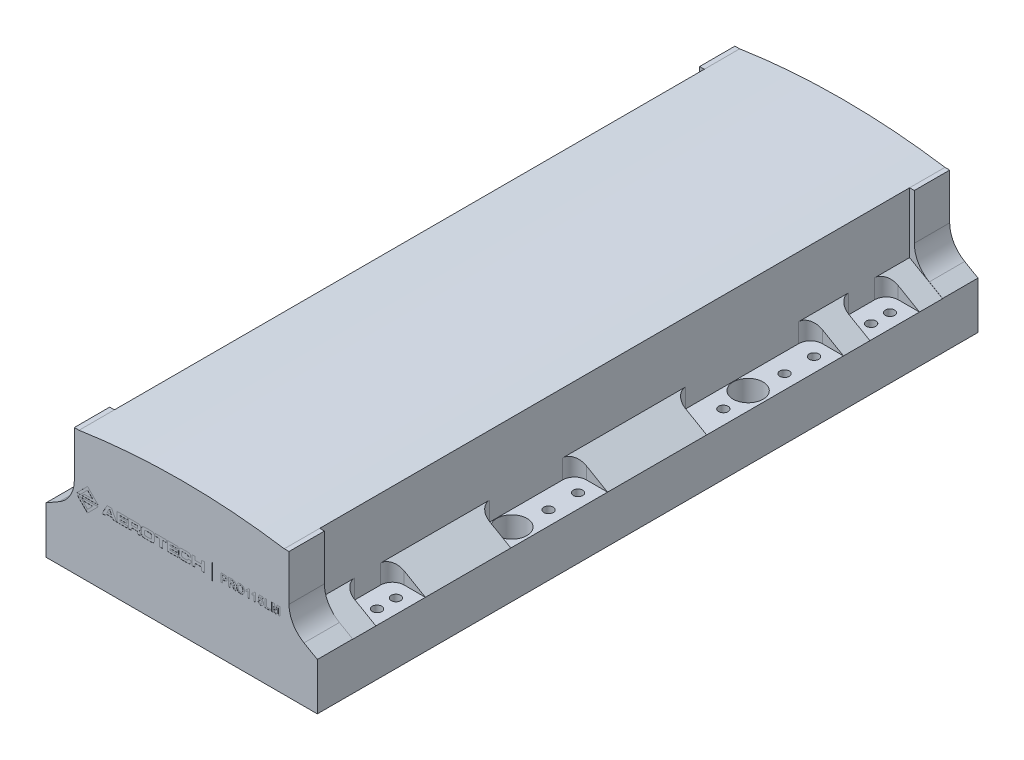
SolidWorks part; units mm, degrees
material "6061 Alloy"
ref_plane "Front" through (0, 0, 0) normal (0, 0, 1) x (1, 0, 0)
ref_plane "Top" through (0, 0, 0) normal (0, 1, 0) x (1, 0, 0)
ref_plane "Right" through (0, 0, 0) normal (1, 0, 0) x (0, 0, -1)
ref_plane "Plane1" through (0, 0, -7.24) normal (0, 0, 1) x (1, 0, 0)
sketch "Sketch1" plane through (0, 0, 0) normal (0, 0, 1) x (1, 0, 0)
  line L0 (-57.5, 0) -> (57.5, 0)
  line L1 (57.5, 0) -> (57.5, 20.9171)
  line L3 (43.5, 29) -> (43.5, 54.6346)
  line L5 (0, 0) -> (0, 146.388) construction
  line L6 (-43.5, 29) -> (-43.5, 54.6346)
  line L7 (43.5, 29) -> (57.5, 20.9171)
  line L8 (-57.5, 0) -> (-57.5, 20.9171)
  line L9 (-43.5, 29) -> (-57.5, 20.9171)
  arc A0 (43.5, 54.6346) -> (-43.5, 54.6346) centre (0, -228.22) ccw
  point P9 (0, 57.96)
  dimension "D7" = 572.36
  dimension "D1" = 115
  dimension "D2" = 60
  dimension "D4" = 29
  dimension "D5" = 87
  dimension "D6" = 60
  dimension "D8" = 228.22
extrude "Base" add sketch "Sketch1" along normal mid plane 250
ref_plane "Plane2" through (0, 57.96, 0) normal (0, 1, 0) x (1, 0, 0)
sketch "Sketch84" plane through (0, 57.96, 0) normal (0, 1, 0) x (-1, 0, 0)
  line L0 (0, 125) -> (0, -125) construction
  line L3 (0, 0) -> (-57.5, 0) construction
  line L6 (-57.5, 125) -> (-57.5, -125) construction
  circle A0 centre (-50, 50) radius 3.3782
  circle A1 centre (50, 50) radius 3.3782
  circle A2 centre (50, -50) radius 3.3782
  circle A3 centre (-50, -50) radius 3.3782
  dimension "D1" = 6.7564
  dimension "D2" = 50
  dimension "D3" = 100
extrude "Cut-Extrude17" cut sketch "Sketch84" against normal through all
sketch "Sketch121" plane through (0, 57.96, 0) normal (0, 1, 0) x (1, 0, 0)
  line L0 (0, 125) -> (0, -125) construction
  line L1 (0, 0) -> (-58.1047, 0) construction
  circle A0 centre (50, 100) radius 3.3782
  circle A1 centre (-50, 100) radius 3.3782
  dimension "D1" = 6.7564
  dimension "D2" = 100
  dimension "D3" = 100
extrude "Cut-Extrude33" [suppressed] cut sketch "Sketch121" against normal through all
sketch "Sketch85" [suppressed] plane through (0, 57.96, 0) normal (0, 1, 0) x (-1, 0, 0)
  line L4 (0, 125) -> (0, -125) construction
  circle A0 centre (-50, -100) radius 6.35
  circle A2 centre (50, -100) radius 6.35
  dimension "D1" = 12.7
extrude "Cut-Extrude18" [suppressed] cut sketch "Sketch85" against normal offset from surface (49.96 mm away) 8
pattern_linear "LPattern3" [suppressed] count 2 spacing 50
mirror "Mirror3" [suppressed] about plane through (0, 0, 0) normal (0, 0, 1)
sketch "Sketch119" plane through (0, 57.96, 0) normal (0, 1, 0) x (1, 0, 0)
  line L0 (-50.8, 50.8) -> (50.8, -50.8) construction
  line L1 (-50.8, 50.8) -> (50.8, 50.8) construction
  line L2 (-50.8, 50.8) -> (-50.8, -50.8) construction
  line L3 (-50.8, -50.8) -> (50.8, -50.8) construction
  line L4 (50.8, 50.8) -> (50.8, -50.8) construction
  circle A0 centre (50.8, 50.8) radius 3.38
  circle A1 centre (-50.8, 50.8) radius 3.38
  circle A2 centre (-50.8, -50.8) radius 3.38
  circle A3 centre (50.8, -50.8) radius 3.38
  dimension "D1" = 6.76
  dimension "D2" = 101.6
extrude "Cut-Extrude31" cut sketch "Sketch119" against normal through all
sketch "Sketch120" plane through (0, 57.96, 0) normal (0, 1, 0) x (1, 0, 0)
  line L0 (-57.5, -125) -> (-57.5, 125) construction
  line L3 (0, 0) -> (-60.7636, 0) construction
  line L5 (0, -113.1077) -> (0, 113.1077) construction
  circle A0 centre (-50.8, 50.8) radius 4.765 construction
  circle A1 centre (-50, 50) radius 5 construction
  circle A2 centre (-50.8, 50.8) radius 5.27 construction
  circle A3 centre (-50.01, 50.0636) radius 6.35
  circle A4 centre (50.01, 50.0636) radius 6.35
  circle A5 centre (-50.01, -50.0636) radius 6.35
  circle A6 centre (50.01, -50.0636) radius 6.35
  dimension "D2" = 9.53
  dimension "D3" = 10
  dimension "D4" = 10.54
  dimension "D5" = 12.7
  dimension "D6" = 1.14
extrude "Cut-Extrude32" cut sketch "Sketch120" against normal offset from surface (49.96 mm away) 8 up to face at (50.4006, 0, -50.4006)
hole_wizard "CBORE for 1/4 Socket Head Cap Screw1" [suppressed] positions "Sketch136" profile "Sketch137" counterbore size "1/4" standard "ANSI Inch"
sketch "Sketch136" plane through (0, 57.96, 0) normal (0, 1, 0) x (1, 0, 0)
  line L0 (0, 135.5467) -> (0, 0) construction
  line L1 (0, 0) -> (-73.2487, 0) construction
  point P0 (-50.8, 177.8)
  point P9 (50.8, 177.8)
  point P10 (50.8, -177.8)
  point P11 (-50.8, -177.8)
  dimension "D1" = 101.6
  dimension "D2" = 457.2
sketch "Sketch137" plane through (-50.8, 57.96, -177.8) normal (1, 0, 0) x (0, 0, 1)
  line L0 (0, 0) -> (0, 57.96)
  line L1 (0, 57.96) -> (3.3782, 57.96)
  line L3 (3.3782, 57.96) -> (3.3782, 49.96)
  line L4 (3.3782, 49.96) -> (5.2451, 49.96)
  line L5 (5.2451, 49.96) -> (5.2451, 0)
  line L7 (5.2451, 0) -> (0, 0)
  line L11 (0, -6.35) -> (0, 107.95) construction
  dimension "Thru Hole Dia." = 6.7564
  dimension "Thru Hole Depth" = 57.96
  dimension "C'Bore Dia." = 10.4902
  dimension "C'Bore Depth" = 49.96
hole_wizard "CBORE for 1/4 Socket Head Cap Screw2" [suppressed] positions "Sketch138" profile "Sketch139" counterbore size "1/4" standard "ANSI Inch"
sketch "Sketch138" plane through (0, 57.96, 0) normal (0, -1, 0) x (-1, 0, 0)
  line L0 (0, -99.0681) -> (0, 0) construction
  line L1 (0, 0) -> (-32.0031, 0) construction
  point P0 (-50.8, 330.2)
  point P9 (50.8, 330.2)
  point P13 (50.8, -330.2)
  point P14 (-50.8, -330.2)
  dimension "D1" = 101.6
  dimension "D2" = 660.4
sketch "Sketch139" plane through (50.8, 57.96, -330.2) normal (1, 0, 0) x (0, 0, 1)
  line L0 (0, 0) -> (0, 57.96)
  line L1 (0, 57.96) -> (3.3782, 57.96)
  line L3 (3.3782, 57.96) -> (3.3782, 49.96)
  line L4 (3.3782, 49.96) -> (5.2451, 49.96)
  line L5 (5.2451, 49.96) -> (5.2451, 0)
  line L7 (5.2451, 0) -> (0, 0)
  line L11 (0, -6.35) -> (0, 107.95) construction
  dimension "Thru Hole Dia." = 6.7564
  dimension "Thru Hole Depth" = 57.96
  dimension "C'Bore Dia." = 10.4902
  dimension "C'Bore Depth" = 49.96
sketch "Sketch23" plane through (0, 0, 125) normal (0, 0, 1) x (1, 0, 0)
  line L0 (-15, 0) -> (15, 0)
  line L1 (-15, 1) -> (15, 1)
  line L2 (-57.5, 0) -> (57.5, 0) construction
  line L3 (0, 0) -> (0, 32.8248) construction
  line L4 (15, 1) -> (15, 0)
  line L5 (-15, 1) -> (-15, 0)
  dimension "D1" = 1
  dimension "D2" = 30
extrude "Lower Pads" cut sketch "Sketch23" against normal through all
sketch "Sketch86" plane through (0, 0, 125) normal (0, 0, 1) x (1, 0, 0)
  line L0 (-57.5, 54.6346) -> (-43.5, 54.6346)
  line L1 (-57.5, 1.021) -> (57.5, 1.021)
  line L2 (-57.5, 1.021) -> (-57.5, 54.6346)
  line L4 (57.5, 1.021) -> (57.5, 54.6346)
  line L5 (-57.5, 0) -> (-15, 0) construction
  line L7 (43.5, 54.6346) -> (57.5, 54.6346)
  line L8 (0, 0) -> (0, 61.021) construction
  line L9 (-57.5, 20.9171) -> (-57.5, 0) construction
  line L10 (57.5, 0) -> (57.5, 20.9171) construction
  arc A0 (43.5, 54.6346) -> (-43.5, 54.6346) centre (0, -228.22) ccw
  arc A1 (43.5, 54.6346) -> (-43.5, 54.6346) centre (0, -228.22) ccw construction
  dimension "D5" = 1.021
extrude "Extrude1" add sketch "Sketch86" along normal blind 15
sketch "Sketch87" plane through (0, 0, -125) normal (0, 0, -1) x (-1, 0, 0)
  line L0 (57.5, 20.9171) -> (57.5, 0) construction
  line L1 (-57.5, 54.6346) -> (-43.5, 54.6346)
  line L2 (-57.5, 54.6346) -> (-57.5, 1.021)
  line L3 (-57.5, 1.021) -> (57.5, 1.021)
  line L4 (57.5, 54.6346) -> (57.5, 1.021)
  line L5 (57.5, 1.021) -> (-57.5, 1.021) construction
  line L6 (43.5, 54.6346) -> (57.5, 54.6346)
  arc A0 (43.5, 54.6346) -> (-43.5, 54.6346) centre (0, -228.22) ccw
  arc A1 (43.5, 54.6346) -> (-43.5, 54.6346) centre (0, -228.22) ccw construction
extrude "Extrude2" add sketch "Sketch87" along normal blind 15
sketch "Sketch97" plane through (0, 57.96, 0) normal (0, 1, 0) x (-1, 0, 0)
  line L0 (57.5, 125) -> (57.5, -125) construction
  line L1 (57.5, -25) -> (48.5, -25)
  line L2 (57.5, -25) -> (57.5, -83)
  line L3 (57.5, -83) -> (48.5, -83)
  line L4 (43.5, -30) -> (43.5, -78)
  line L5 (43.5, 125) -> (43.5, -125) construction
  line L6 (0, 0) -> (-57.5, 0) construction
  line L7 (-57.5, 125) -> (-57.5, -125) construction
  line L8 (0, 0) -> (0, -140) construction
  line L9 (-43.5, -140) -> (-57.5, -140) construction
  line L11 (-43.5, -30) -> (-43.5, -78)
  line L12 (-57.5, -83) -> (-48.5, -83)
  line L13 (-57.5, -25) -> (-57.5, -83)
  line L14 (-57.5, -25) -> (-48.5, -25)
  line L15 (-57.5, 17) -> (-48.5, 17)
  line L16 (-57.5, 17) -> (-57.5, 58)
  line L17 (-57.5, 58) -> (-48.5, 58)
  line L18 (-43.5, 22) -> (-43.5, 53)
  line L19 (43.5, 22) -> (43.5, 53)
  line L20 (57.5, 58) -> (48.5, 58)
  line L21 (57.5, 17) -> (57.5, 58)
  line L22 (57.5, 17) -> (48.5, 17)
  arc A0 (43.5, -78) -> (48.5, -83) centre (48.5, -78) ccw
  arc A1 (43.5, -30) -> (48.5, -25) centre (48.5, -30) cw
  arc A2 (-43.5, -30) -> (-48.5, -25) centre (-48.5, -30) ccw
  arc A3 (-43.5, -78) -> (-48.5, -83) centre (-48.5, -78) cw
  arc A4 (-43.5, 53) -> (-48.5, 58) centre (-48.5, 53) ccw
  arc A5 (-43.5, 22) -> (-48.5, 17) centre (-48.5, 22) cw
  arc A6 (43.5, 22) -> (48.5, 17) centre (48.5, 22) ccw
  arc A7 (43.5, 53) -> (48.5, 58) centre (48.5, 53) cw
  dimension "D3" = 5
  dimension "D1" = 25
  dimension "D2" = 83
  dimension "D4" = 17
  dimension "D5" = 58
extrude "Cut-Extrude21" cut sketch "Sketch97" against normal up to vertex (54.671 mm away)
sketch "Sketch98" plane through (0, 0, 140) normal (0, 0, 1) x (1, 0, 0)
  line L0 (57.5, 54.6346) -> (45.5, 54.6346)
  line L1 (57.5, 54.6346) -> (43.5, 54.6346) construction
  line L2 (45.5, 54.6346) -> (45.5, 27.9282)
  line L3 (45.5, 27.9282) -> (57.5, 21)
  line L4 (57.5, 1.021) -> (57.5, 54.6346) construction
  line L5 (57.5, 21) -> (57.5, 54.6346)
  line L6 (15, 0) -> (57.5, 0) construction
  line L7 (0, 0) -> (0, 57.96) construction
  line L9 (-57.5, 21) -> (-57.5, 54.6346)
  line L10 (-45.5, 27.9282) -> (-57.5, 21)
  line L11 (-45.5, 54.6346) -> (-45.5, 27.9282)
  line L12 (-57.5, 54.6346) -> (-45.5, 54.6346)
  arc A0 (43.5, 54.6346) -> (-43.5, 54.6346) centre (0, -228.22) ccw construction
  dimension "D1" = 12
  dimension "D2" = 21
  dimension "D3" = 120
extrude "Cut-Extrude22" cut sketch "Sketch98" against normal through all
fillet "Fillet1" radius 12.7 4 edges at (-45.5, 27.9282, 132.5) (-45.5, 27.9282, -132.5) (45.5, 27.9282, -132.5) (45.5, 27.9282, 132.5)
chamfer "Chamfer1" distance 1 angle 45 4 edges at (-15, 0, 0) (15, 0, 0) (-57.5, 0, 0) (57.5, 0, 0)
sketch "Sketch103" [suppressed] plane through (0, 57.96, 0) normal (0, 1, 0) x (1, 0, 0)
  line L0 (-50, 0) -> (50, 0) construction
  line L1 (-57.5, -17) -> (-57.5, 25) construction
  circle A0 centre (-50, 0) radius 6.35
  circle A1 centre (50, 0) radius 6.35
  dimension "D1" = 12.7
  dimension "D2" = 7.5
extrude "Cut-Extrude26" [suppressed] cut sketch "Sketch103" against normal up to surface (49.96 mm away)
sketch "Sketch104" [suppressed] plane through (0, 8, 0) normal (0, 1, 0) x (1, 0, 0)
  circle A0 centre (50, 0) radius 3.3782
  circle A1 centre (-50, 0) radius 3.3782
  circle A3 centre (50, 50) radius 3.3782 construction
extrude "Cut-Extrude27" [suppressed] cut sketch "Sketch104" against normal through all
sketch "Sketch107" plane through (0, 1, 0) normal (0, -1, 0) x (1, 0, 0)
  circle A0 centre (0, 0) radius 4.007
  dimension "D1" = 8.014
extrude "Cut-Extrude30" cut sketch "Sketch107" against normal blind 9
pattern_linear "LPattern2" count 4 spacing 25 along (0, 0, 1) of "Cut-Extrude30"
mirror "Mirror2" about plane through (0, 0, 0) normal (0, 0, 1) of "LPattern2"
hole_wizard "M4x0.7 Tapped Hole2" positions "Sketch109" profile "Sketch108" tap size "M4x0.7" standard "ANSI Metric"
sketch "Sketch109" plane through (0, 20.9171, 0) normal (0, 1, 0) x (-1, 0, 0)
  line L5 (0, 0) -> (116.5246, 0) construction
  line L8 (0, 129.449) -> (0, -129.449) construction
  line L10 (51.5, -76.5) -> (51.5, -64) construction
  line L16 (57.5, -83) -> (57.5, -25) construction
  line L18 (-51.5, -76.5) -> (-51.5, -64) construction
  line L19 (-51.5, 36) -> (-51.5, 23.5) construction
  line L22 (51.5, 36) -> (51.5, 23.5) construction
  point P23 (51.5, -64)
  point P48 (51.5, -76.5)
  point P75 (-51.5, -76.5)
  point P76 (-51.5, -64)
  point P77 (-51.5, 36)
  point P78 (-51.5, 23.5)
  point P83 (51.5, 36)
  point P84 (51.5, 23.5)
  dimension "D1" = 12.5
  dimension "D3" = 6
  dimension "D4" = 23.5
  dimension "D2" = 64
sketch "Sketch108" plane through (-51.5, 20.9171, -64) normal (1, 0, 0) x (0, 0, 1)
  line L0 (0, 0) -> (0, 13.0914)
  line L1 (0, 13.0914) -> (1.65, 12.1)
  line L2 (1.65, 12.1) -> (1.65, 10)
  line L3 (1.65, 10) -> (2, 10)
  line L4 (2, 10) -> (2, 0)
  line L5 (2, 0) -> (0, 0)
  line L10 (0, 13.0914) -> (-1.65, 12.1) construction
  line L11 (0, -6.35) -> (0, 107.95) construction
  dimension "Tap Drill Dia." = 3.3
  dimension "Tap Drill Depth" = 12.1
  dimension "Thread Major Dia." = 4
  dimension "Thread Depth" = 10
  dimension "Drill Angle" = 118
sketch "Sketch122" plane through (0, 57.96, 0) normal (0, 1, 0) x (1, 0, 0)
  line L0 (-43.5, -125) -> (-43.5, 125) construction
  line L1 (-57.5, 115.2) -> (-48.5, 115.2)
  line L2 (-57.5, 115.2) -> (-57.5, 94.2)
  line L3 (-57.5, 94.2) -> (-48.5, 94.2)
  line L4 (-43.5, 110.2) -> (-43.5, 99.2)
  line L7 (0, 0) -> (-171.2058, 0) construction
  line L8 (-57.5, 83) -> (-57.5, 25) construction
  line L9 (0, -271.3829) -> (0, 271.3829) construction
  line L16 (57.5, 94.2) -> (48.5, 94.2)
  line L17 (57.5, 115.2) -> (48.5, 115.2)
  line L22 (43.5, 110.2) -> (43.5, 99.2)
  line L24 (57.5, 115.2) -> (57.5, 94.2)
  line L28 (57.5, -115.2) -> (48.5, -115.2)
  line L29 (57.5, -115.2) -> (57.5, -94.2)
  line L30 (57.5, -94.2) -> (48.5, -94.2)
  line L31 (43.5, -110.2) -> (43.5, -99.2)
  line L38 (-57.5, -94.2) -> (-48.5, -94.2)
  line L39 (-57.5, -115.2) -> (-48.5, -115.2)
  line L44 (-43.5, -110.2) -> (-43.5, -99.2)
  line L46 (-57.5, -115.2) -> (-57.5, -94.2)
  arc A0 (48.5, -94.2) -> (43.5, -99.2) centre (48.5, -99.2) ccw
  arc A1 (48.5, -115.2) -> (43.5, -110.2) centre (48.5, -110.2) cw
  arc A2 (-48.5, -115.2) -> (-43.5, -110.2) centre (-48.5, -110.2) ccw
  arc A3 (-48.5, -94.2) -> (-43.5, -99.2) centre (-48.5, -99.2) cw
  arc A4 (48.5, 94.2) -> (43.5, 99.2) centre (48.5, 99.2) cw
  arc A5 (48.5, 115.2) -> (43.5, 110.2) centre (48.5, 110.2) ccw
  arc A6 (-48.5, 94.2) -> (-43.5, 99.2) centre (-48.5, 99.2) ccw
  arc A7 (-48.5, 115.2) -> (-43.5, 110.2) centre (-48.5, 110.2) cw
  point P35 (43.5, -94.2)
  point P38 (43.5, -115.2)
  point P41 (-43.5, -115.2)
  point P44 (-43.5, -94.2)
  point P47 (43.5, 94.2)
  point P50 (43.5, 115.2)
  point P53 (-43.5, 94.2)
  point P56 (-43.5, 115.2)
  dimension "D3" = 5
  dimension "D2" = 94.2
  dimension "D4" = 115.2
extrude "Cut-Extrude34" cut sketch "Sketch122" against normal up to surface (37.0429 mm away) up to face at (-51.5, 20.9171, -62)
hole_wizard "M4x0.7 Tapped Hole5" positions "Sketch124" profile "Sketch123" tap size "M4x0.7" standard "ANSI Metric"
sketch "Sketch124" plane through (0, 20.9171, 0) normal (0, 1, 0) x (1, 0, 0)
  line L2 (-51.5, 108.7) -> (-51.5, 100.7) construction
  line L6 (-57.5, 94.2) -> (-57.5, 115.2) construction
  line L8 (0, 0) -> (-155.8698, 0) construction
  line L11 (0, 0) -> (0, 209.1535) construction
  line L12 (-57.5, 115.2) -> (-48.5, 115.2) construction
  point P0 (-51.5, 108.7)
  point P2 (-51.5, 100.7)
  point P33 (51.5, 100.7)
  point P34 (51.5, 108.7)
  point P36 (-51.5, -108.7)
  point P37 (-51.5, -100.7)
  point P38 (51.5, -108.7)
  point P39 (51.5, -100.7)
  dimension "D1" = 8
  dimension "D2" = 6
  dimension "D3" = 6.5
sketch "Sketch123" plane through (-51.5, 20.9171, -108.7) normal (1, 0, 0) x (0, 0, 1)
  line L0 (0, 0) -> (0, 13.0914)
  line L1 (0, 13.0914) -> (1.65, 12.1)
  line L2 (1.65, 12.1) -> (1.65, 10)
  line L3 (1.65, 10) -> (2, 10)
  line L4 (2, 10) -> (2, 0)
  line L5 (2, 0) -> (0, 0)
  line L10 (0, 13.0914) -> (-1.65, 12.1) construction
  line L11 (0, -6.35) -> (0, 107.95) construction
  dimension "Tap Drill Dia." = 3.3
  dimension "Tap Drill Depth" = 12.1
  dimension "Thread Major Dia." = 4
  dimension "Thread Depth" = 10
  dimension "Drill Angle" = 118
sketch "Sketch115" plane through (0, 57.96, 0) normal (0, 1, 0) x (1, 0, 0)
  line L0 (-51.85, 125) -> (-57.5, 125) construction
  line L1 (-57.5, -89.5) -> (-43.5, -89.5)
  line L2 (-57.5, -89.5) -> (-57.5, -115)
  line L3 (-57.5, -115) -> (-43.5, -115)
  line L4 (-43.5, -89.5) -> (-43.5, -115)
  line L7 (0, 0) -> (-69.7916, 0) construction
  line L8 (-43.5, 89.5) -> (-43.5, 115)
  line L9 (-57.5, 115) -> (-43.5, 115)
  line L10 (-57.5, 89.5) -> (-57.5, 115)
  line L11 (-57.5, 89.5) -> (-43.5, 89.5)
  line L12 (0, 0) -> (0, -483.8343) construction
  line L13 (57.5, 89.5) -> (43.5, 89.5)
  line L14 (57.5, 89.5) -> (57.5, 115)
  line L15 (57.5, 115) -> (43.5, 115)
  line L16 (43.5, 89.5) -> (43.5, 115)
  line L17 (43.5, -89.5) -> (43.5, -115)
  line L18 (57.5, -115) -> (43.5, -115)
  line L19 (57.5, -89.5) -> (57.5, -115)
  line L20 (57.5, -89.5) -> (43.5, -89.5)
  line L21 (43.5, -22) -> (43.5, -53) construction
  line L22 (57.5, -125) -> (57.5, -115.2) construction
  dimension "D1" = 10
  dimension "D2" = 25.5
extrude "Extrude7" [suppressed] cut sketch "Sketch115" against normal up to surface (37.0429 mm away)
fillet "Fillet2" [suppressed] radius 5
hole_wizard "M4x0.7 Tapped Hole4" [suppressed] positions "Sketch116" profile "Sketch117" tap size "M4x0.7" standard "ANSI Metric"
sketch "Sketch116" [suppressed] plane through (0, 20.9171, 0) normal (0, 1, 0) x (-1, 0, 0)
  line L0 (-51.5, -76.5) -> (-51.5, -64) construction
  line L2 (-51.5, 221) -> (-51.5, 233.5) construction
  line L7 (0, -97.8) -> (0, 0) construction
  line L8 (0, 0) -> (-90.3431, 0) construction
  line L9 (-48.5, 214.5) -> (-57.5, 214.5) construction
  point P0 (-51.5, 221)
  point P5 (-51.5, 233.5)
  point P49 (51.5, 233.5)
  point P50 (51.5, 221)
  point P51 (-51.5, -233.5)
  point P52 (-51.5, -221)
  point P53 (51.5, -233.5)
  point P54 (51.5, -221)
  dimension "D1" = 6.5
sketch "Sketch117" plane through (51.5, 20.9171, 221) normal (1, 0, 0) x (0, 0, 1)
  line L0 (0, 0) -> (0, 13.0914)
  line L1 (0, 13.0914) -> (1.65, 12.1)
  line L2 (1.65, 12.1) -> (1.65, 10)
  line L3 (1.65, 10) -> (2, 10)
  line L4 (2, 10) -> (2, 0)
  line L5 (2, 0) -> (0, 0)
  line L10 (0, 13.0914) -> (-1.65, 12.1) construction
  line L11 (0, -6.35) -> (0, 107.95) construction
  dimension "Tap Drill Dia." = 3.3
  dimension "Tap Drill Depth" = 12.1
  dimension "Thread Major Dia." = 4
  dimension "Thread Depth" = 10
  dimension "Drill Angle" = 118
hole_wizard "M4x0.7 Tapped Hole6" positions "Sketch134" profile "Sketch133" tap size "M4x0.7" standard "ANSI Metric"
sketch "Sketch134" plane through (0, 20.9171, 0) normal (0, 1, 0) x (-1, 0, 0)
  point P0 (-51.5, -38.0746)
  point P2 (51.5, -38.0746)
  dimension "D1" = 38.0746
sketch "Sketch133" plane through (51.5, 20.9171, -38.0746) normal (1, 0, 0) x (0, 0, 1)
  line L0 (0, 0) -> (0, 11.0914)
  line L1 (0, 11.0914) -> (1.65, 10.1)
  line L2 (1.65, 10.1) -> (1.65, 8)
  line L3 (1.65, 8) -> (2, 8)
  line L4 (2, 8) -> (2, 0)
  line L5 (2, 0) -> (0, 0)
  line L10 (0, 11.0914) -> (-1.65, 10.1) construction
  line L11 (0, -6.35) -> (0, 107.95) construction
  dimension "Tap Drill Dia." = 3.3
  dimension "Tap Drill Depth" = 10.1
  dimension "Thread Major Dia." = 4
  dimension "Thread Depth" = 8
  dimension "Drill Angle" = 118
ref_plane "Neg Elec Limit" through (0, 0, 30) normal (0, 0, 1) x (1, 0, 0)
ref_plane "Neg Hard Stop" through (0, 0, 37.5) normal (0, 0, 1) x (1, 0, 0)
ref_plane "Neg Nominal Travel Limit" through (0, 0, 25) normal (0, 0, 1) x (1, 0, 0)
ref_plane "Pos Nominal Travel Limit" through (0, 0, -25) normal (0, 0, 1) x (1, 0, 0)
ref_plane "Pos Elec Limit" through (0, 0, -30) normal (0, 0, 1) x (1, 0, 0)
ref_plane "Pos Hard Stop" through (0, 0, -37.5) normal (0, 0, 1) x (1, 0, 0)
sketch "Sketch140" plane through (0, 0, 140) normal (0, 0, 1) x (1, 0, 0)
  line L0 (9.7306, 30.9175) -> (12.9223, 30.9175) construction
  line L1 (-33.783, 28.9203) -> (137.8803, 28.9203) construction
  line L2 (-1.3394, 148.5268) -> (-1.3394, 202.5426) construction
  line L3 (16.3009, 30.9523) -> (13.1692, 30.9523) construction
  line L4 (-44.3894, 35.8141) -> (41.7106, 35.8141) construction
  line L5 (-44.3894, 35.8141) -> (-44.3894, 26.021) construction
  line L6 (-44.3894, 26.021) -> (41.7106, 26.021) construction
  line L7 (41.7106, 35.8141) -> (41.7106, 26.021) construction
  line L9 (-57.5, 1.021) -> (57.5, 1.021) construction
  text T0 "<b>PRO115LM</b>" font "Arial" height 3.5
  point P10 (-1.2589, 30.8909)
  point P13 (-1.3394, 26.021)
  line B0 (-39.9006, 26.021) -> (-35.3807, 30.5877)
  line B1 (-35.3807, 30.5877) -> (-42.2558, 30.5668)
  line B2 (-42.2558, 30.5668) -> (-41.2744, 29.5804)
  line B3 (-41.2744, 29.5804) -> (-37.7053, 29.596)
  line B4 (-37.7053, 29.596) -> (-39.9056, 27.4109)
  line B5 (-39.9056, 27.4109) -> (-43.0364, 30.5668)
  line B6 (-43.0364, 30.5668) -> (-44.3894, 30.5617)
  line B7 (-44.3894, 30.5617) -> (-39.9006, 26.021)
  line B8 (-39.9006, 35.8141) -> (-35.3807, 31.2476)
  line B9 (-35.3807, 31.2476) -> (-42.2558, 31.2686)
  line B10 (-42.2558, 31.2686) -> (-41.2744, 32.255)
  line B11 (-41.2744, 32.255) -> (-37.7053, 32.2392)
  line B12 (-37.7053, 32.2392) -> (-39.9056, 34.4244)
  line B13 (-39.9056, 34.4244) -> (-43.0364, 31.2686)
  line B14 (-43.0364, 31.2686) -> (-44.3894, 31.2735)
  line B15 (-44.3894, 31.2735) -> (-39.9006, 35.8141)
  line B16 (-28.9992, 28.9203) -> (-29.3465, 29.5948)
  line B17 (-29.3465, 29.5948) -> (-32.0262, 29.5948)
  line B18 (-32.0262, 29.5948) -> (-32.3735, 28.9203)
  line B19 (-32.3735, 28.9203) -> (-33.783, 28.9203)
  line B20 (-33.783, 28.9203) -> (-31.6346, 32.9147)
  line B21 (-31.6346, 32.9147) -> (-29.7174, 32.9147)
  line B22 (-29.7174, 32.9147) -> (-27.5984, 28.9203)
  line B23 (-27.5984, 28.9203) -> (-28.9992, 28.9203)
  line B24 (-29.7796, 30.4717) -> (-30.5602, 31.9855)
  line B25 (-30.5602, 31.9855) -> (-30.8064, 31.9855)
  line B26 (-30.8064, 31.9855) -> (-31.5871, 30.4717)
  line B27 (-31.5871, 30.4717) -> (-29.7796, 30.4717)
  line B28 (-27.3996, 32.9147) -> (-22.9105, 32.9147)
  line B29 (-22.9105, 32.9147) -> (-22.9105, 31.9781)
  line B30 (-22.9105, 31.9781) -> (-26.1855, 31.9781)
  line B31 (-26.1855, 31.9781) -> (-26.1855, 31.401)
  line B32 (-26.1855, 31.401) -> (-23.0754, 31.401)
  line B33 (-23.0754, 31.401) -> (-23.0754, 30.5243)
  line B34 (-23.0754, 30.5243) -> (-26.1855, 30.5243)
  line B35 (-26.1855, 30.5243) -> (-26.1855, 29.872)
  line B36 (-26.1855, 29.872) -> (-22.8879, 29.872)
  line B37 (-22.8879, 29.872) -> (-22.8879, 28.9203)
  line B38 (-22.8879, 28.9203) -> (-27.3996, 28.9203)
  line B39 (-27.3996, 28.9203) -> (-27.3996, 32.9147)
  line B40 (-22.4845, 28.9203) -> (-22.4845, 32.9147)
  line B41 (-22.4845, 32.9147) -> (-19.5008, 32.9147)
  line B42 (-17.4858, 29.2903) -> (-17.4858, 28.9203)
  line B43 (-17.4858, 28.9203) -> (-18.6998, 28.9203)
  line B44 (-18.6998, 28.9203) -> (-18.6998, 29.1301)
  line B45 (-19.5097, 29.9321) -> (-21.2478, 29.9321)
  line B46 (-21.2478, 29.9321) -> (-21.2478, 28.9203)
  line B47 (-21.2478, 28.9203) -> (-22.4845, 28.9203)
  line B48 (-21.2478, 30.9288) -> (-19.5127, 30.9288)
  line B49 (-19.5156, 31.9181) -> (-21.2478, 31.9181)
  line B50 (-21.2478, 31.9181) -> (-21.2478, 30.9288)
  line B51 (-11.261, 32.9147) -> (-6.3593, 32.9147)
  line B52 (-6.3593, 32.9147) -> (-6.3593, 31.8956)
  line B53 (-6.3593, 31.8956) -> (-8.1582, 31.8956)
  line B54 (-8.1582, 31.8956) -> (-8.1582, 28.9203)
  line B55 (-8.1582, 28.9203) -> (-9.4547, 28.9203)
  line B56 (-9.4547, 28.9203) -> (-9.4547, 31.8956)
  line B57 (-9.4547, 31.8956) -> (-11.261, 31.8956)
  line B58 (-11.261, 31.8956) -> (-11.261, 32.9147)
  line B59 (-6.0733, 32.9147) -> (-1.5843, 32.9147)
  line B60 (-1.5843, 32.9147) -> (-1.5843, 31.9781)
  line B61 (-1.5843, 31.9781) -> (-4.8593, 31.9781)
  line B62 (-4.8593, 31.9781) -> (-4.8593, 31.401)
  line B63 (-4.8593, 31.401) -> (-1.7492, 31.401)
  line B64 (-1.7492, 31.401) -> (-1.7492, 30.5243)
  line B65 (-1.7492, 30.5243) -> (-4.8593, 30.5243)
  line B66 (-4.8593, 30.5243) -> (-4.8593, 29.872)
  line B67 (-4.8593, 29.872) -> (-1.5618, 29.872)
  line B68 (-1.5618, 29.872) -> (-1.5618, 28.9203)
  line B69 (-1.5618, 28.9203) -> (-6.0733, 28.9203)
  line B70 (-6.0733, 28.9203) -> (-6.0733, 32.9147)
  line B71 (2.6755, 30.4642) -> (3.9102, 30.4642)
  line B72 (3.8449, 31.4834) -> (2.6104, 31.4834)
  line B73 (4.3494, 32.9147) -> (5.6461, 32.9147)
  line B74 (5.6461, 32.9147) -> (5.6461, 31.4834)
  line B75 (5.6461, 31.4834) -> (8.4339, 31.4834)
  line B76 (8.4339, 31.4834) -> (8.4339, 32.9147)
  line B77 (8.4339, 32.9147) -> (9.7306, 32.9147)
  line B78 (9.7306, 32.9147) -> (9.7306, 28.9203)
  line B79 (9.7306, 28.9203) -> (8.4339, 28.9203)
  line B80 (8.4339, 28.9203) -> (8.4339, 30.3668)
  line B81 (8.4339, 30.3668) -> (5.6461, 30.3668)
  line B82 (5.6461, 30.3668) -> (5.6461, 28.9203)
  line B83 (5.6461, 28.9203) -> (4.3494, 28.9203)
  line B84 (4.3494, 28.9203) -> (4.3494, 32.9147)
  line B85 (13.1692, 27.4951) -> (12.9223, 27.4951)
  line B86 (12.9223, 27.4951) -> (12.9223, 34.4095)
  line B87 (12.9223, 34.4095) -> (13.1692, 34.4095)
  line B88 (13.1692, 34.4095) -> (13.1692, 27.4951)
  spline B89 degree 3 poles (-19.5008, 32.9147) (-18.8013, 32.9129) (-18.3824, 32.9059) (-18.2441, 32.894) knots 2 2 2 2 3 3 3 3
  spline B90 degree 3 poles (-18.2441, 32.894) (-18.1057, 32.882) (-17.9724, 32.8365) (-17.8438, 32.7571) knots 3 3 3 3 4 4 4 4
  spline B91 degree 3 poles (-17.8438, 32.7571) (-17.6898, 32.666) (-17.5842, 32.5395) (-17.5268, 32.3778) knots 4 4 4 4 5 5 5 5
  spline B92 degree 3 poles (-17.5268, 32.3778) (-17.4695, 32.2162) (-17.4408, 31.9626) (-17.4408, 31.6177) knots 5 5 5 5 6 6 6 6
  spline B93 degree 3 poles (-17.4408, 31.6177) (-17.4408, 31.3261) (-17.459, 31.1117) (-17.4955, 30.9749) knots 6 6 6 6 7 7 7 7
  spline B94 degree 3 poles (-17.4955, 30.9749) (-17.5321, 30.838) (-17.6009, 30.7278) (-17.7016, 30.6445) knots 7 7 7 7 8 8 8 8
  spline B95 degree 3 poles (-17.7016, 30.6445) (-17.8101, 30.5575) (-17.9744, 30.497) (-18.1936, 30.4632) knots 8 8 8 8 9 9 9 9
  spline B96 degree 3 poles (-18.1936, 30.4632) (-17.9351, 30.4432) (-17.7494, 30.3703) (-17.6369, 30.2442) knots 9 9 9 9 10 10 10 10
  spline B97 degree 3 poles (-17.6369, 30.2442) (-17.5716, 30.1688) (-17.5301, 30.077) (-17.5126, 29.9684) knots 10 10 10 10 11 11 11 11
  spline B98 degree 3 poles (-17.5126, 29.9684) (-17.4947, 29.8599) (-17.4858, 29.6338) (-17.4858, 29.2903) knots 11 11 11 11 12 12 12 12
  spline B99 degree 3 poles (-18.6998, 29.1301) (-18.6998, 29.3531) (-18.7082, 29.5119) (-18.7251, 29.6065) knots 15 15 15 15 16 16 16 16
  spline B100 degree 3 poles (-18.7251, 29.6065) (-18.742, 29.7012) (-18.773, 29.7734) (-18.8184, 29.8225) knots 16 16 16 16 17 17 17 17
  spline B101 degree 3 poles (-18.8184, 29.8225) (-18.864, 29.8698) (-18.9268, 29.8999) (-19.0069, 29.9128) knots 17 17 17 17 18 18 18 18
  spline B102 degree 3 poles (-19.0069, 29.9128) (-19.0869, 29.9256) (-19.2547, 29.9321) (-19.5097, 29.9321) knots 18 18 18 18 19 19 19 19
  spline B103 degree 3 poles (-19.5127, 30.9288) (-19.2133, 30.9348) (-19.0348, 30.9402) (-18.977, 30.9453) knots 1 1 1 1 2 2 2 2
  spline B104 degree 3 poles (-18.977, 30.9453) (-18.9192, 30.9501) (-18.8699, 30.9656) (-18.8286, 30.9916) knots 2 2 2 2 3 3 3 3
  spline B105 degree 3 poles (-18.8286, 30.9916) (-18.7759, 31.0234) (-18.7388, 31.0722) (-18.7173, 31.138) knots 3 3 3 3 4 4 4 4
  spline B106 degree 3 poles (-18.7173, 31.138) (-18.6957, 31.2038) (-18.6848, 31.3034) (-18.6848, 31.4369) knots 4 4 4 4 5 5 5 5
  spline B107 degree 3 poles (-18.6848, 31.4369) (-18.6848, 31.5704) (-18.6972, 31.6695) (-18.7217, 31.7343) knots 5 5 5 5 6 6 6 6
  spline B108 degree 3 poles (-18.7217, 31.7343) (-18.7461, 31.799) (-18.7885, 31.8454) (-18.8493, 31.8733) knots 6 6 6 6 7 7 7 7
  spline B109 degree 3 poles (-18.8493, 31.8733) (-18.8924, 31.8932) (-18.9437, 31.9051) (-19.0034, 31.9091) knots 7 7 7 7 8 8 8 8
  spline B110 degree 3 poles (-19.0034, 31.9091) (-19.0632, 31.913) (-19.2339, 31.916) (-19.5156, 31.9181) knots 8 8 8 8 9 9 9 9
  spline B111 degree 3 poles (-16.0997, 32.9093) (-15.7732, 32.9528) (-15.1716, 32.9748) (-14.2949, 32.9748) knots 11 11 11 11 12 12 12 12
  spline B112 degree 3 poles (-16.9695, 32.2465) (-16.8625, 32.6269) (-16.5728, 32.8478) (-16.0997, 32.9093) knots 10 10 10 10 11 11 11 11
  spline B113 degree 3 poles (-16.9695, 29.5858) (-17.0425, 29.8472) (-17.0791, 30.2994) (-17.0791, 30.9413) (-17.0791, 31.5517) (-17.0425, 31.9867) (-16.9695, 32.2465) knots 8 8 8 8 9 9 9 10 10 10 10
  spline B114 degree 3 poles (-16.0997, 28.9198) (-16.5728, 28.9833) (-16.8625, 29.2051) (-16.9695, 29.5858) knots 7 7 7 7 8 8 8 8
  spline B115 degree 3 poles (-12.4903, 28.9198) (-12.8189, 28.8802) (-13.4164, 28.8605) (-14.283, 28.8605) (-15.1658, 28.8605) (-15.7713, 28.8802) (-16.0997, 28.9198) knots 5 5 5 5 6 6 6 7 7 7 7
  spline B116 degree 3 poles (-11.6206, 29.5858) (-11.7276, 29.2051) (-12.0176, 28.9833) (-12.4903, 28.9198) knots 4 4 4 4 5 5 5 5
  spline B117 degree 3 poles (-11.6206, 32.2465) (-11.5473, 31.9847) (-11.5108, 31.5417) (-11.5108, 30.9174) (-11.5108, 30.2913) (-11.5473, 29.8472) (-11.6206, 29.5858) knots 2 2 2 2 3 3 3 4 4 4 4
  spline B118 degree 3 poles (-12.4903, 32.9093) (-12.0176, 32.8478) (-11.7276, 32.6269) (-11.6206, 32.2465) knots 1 1 1 1 2 2 2 2
  spline B119 degree 3 poles (-14.2949, 32.9748) (-13.4206, 32.9748) (-12.8189, 32.9528) (-12.4903, 32.9093) knots 0 0 0 0 1 1 1 1
  spline B120 degree 3 poles (-13.2069, 31.9019) (-13.3572, 31.9227) (-13.7188, 31.9331) (-14.292, 31.9331) knots 13 13 13 13 14 14 14 14
  spline B121 degree 3 poles (-12.8837, 31.7426) (-12.9491, 31.828) (-13.0567, 31.881) (-13.2069, 31.9019) knots 12 12 12 12 13 13 13 13
  spline B122 degree 3 poles (-12.777, 31.4376) (-12.7969, 31.5734) (-12.8324, 31.6753) (-12.8837, 31.7426) knots 11 11 11 11 12 12 12 12
  spline B123 degree 3 poles (-12.786, 30.2801) (-12.7603, 30.3861) (-12.7473, 30.5612) (-12.7473, 30.8052) (-12.7473, 31.091) (-12.7574, 31.3017) (-12.777, 31.4376) knots 9 9 9 9 10 10 10 11 11 11 11
  spline B124 degree 3 poles (-12.9312, 30.0375) (-12.86, 30.0931) (-12.8117, 30.1737) (-12.786, 30.2801) knots 8 8 8 8 9 9 9 9
  spline B125 degree 3 poles (-13.296, 29.9214) (-13.1319, 29.9392) (-13.0103, 29.9779) (-12.9312, 30.0375) knots 7 7 7 7 8 8 8 8
  spline B126 degree 3 poles (-15.3565, 29.9302) (-15.1724, 29.9064) (-14.8157, 29.8946) (-14.2859, 29.8946) (-13.7899, 29.8946) (-13.4599, 29.9034) (-13.296, 29.9214) knots 5 5 5 5 6 6 6 7 7 7 7
  spline B127 degree 3 poles (-15.8039, 30.2785) (-15.7546, 30.074) (-15.6054, 29.9581) (-15.3565, 29.9302) knots 4 4 4 4 5 5 5 5
  spline B128 degree 3 poles (-15.7714, 31.6221) (-15.8188, 31.4862) (-15.8425, 31.2149) (-15.8425, 30.8082) (-15.8425, 30.5642) (-15.8296, 30.3876) (-15.8039, 30.2785) knots 2 2 2 2 3 3 3 4 4 4 4
  spline B129 degree 3 poles (-15.4719, 31.8825) (-15.6241, 31.8448) (-15.724, 31.7579) (-15.7714, 31.6221) knots 1 1 1 1 2 2 2 2
  spline B130 degree 3 poles (-14.292, 31.9331) (-14.9464, 31.9331) (-15.3395, 31.9162) (-15.4719, 31.8825) knots 0 0 0 0 1 1 1 1
  spline B131 degree 3 poles (3.9102, 30.4642) (3.9163, 30.2698) (3.9194, 30.1437) (3.9194, 30.0862) knots 1 1 1 1 2 2 2 2
  spline B132 degree 3 poles (3.9194, 30.0862) (3.9194, 29.7768) (3.8729, 29.5349) (3.78, 29.3603) knots 2 2 2 2 3 3 3 3
  spline B133 degree 3 poles (3.78, 29.3603) (3.6773, 29.1658) (3.4764, 29.034) (3.1776, 28.9645) knots 3 3 3 3 4 4 4 4
  spline B134 degree 3 poles (3.1776, 28.9645) (2.8793, 28.8951) (2.3635, 28.8605) (1.6299, 28.8605) knots 4 4 4 4 5 5 5 5
  spline B135 degree 3 poles (1.6299, 28.8605) (0.8587, 28.8605) (0.3091, 28.8745) (-0.018, 28.9019) knots 5 5 5 5 6 6 6 6
  spline B136 degree 3 poles (-0.018, 28.9019) (-0.3452, 28.9295) (-0.5917, 28.9859) (-0.7581, 29.0712) knots 6 6 6 6 7 7 7 7
  spline B137 degree 3 poles (-0.7581, 29.0712) (-0.9064, 29.1462) (-1.0171, 29.2483) (-1.0901, 29.3767) knots 7 7 7 7 8 8 8 8
  spline B138 degree 3 poles (-1.0901, 29.3767) (-1.1632, 29.5054) (-1.2107, 29.6825) (-1.2324, 29.9081) knots 8 8 8 8 9 9 9 9
  spline B139 degree 3 poles (-1.2324, 29.9081) (-1.2505, 30.0882) (-1.2589, 30.4159) (-1.2589, 30.8909) knots 9 9 9 9 10 10 10 10
  spline B140 degree 3 poles (-1.2589, 30.8909) (-1.2589, 31.3538) (-1.2505, 31.6878) (-1.2324, 31.8927) knots 10 10 10 10 11 11 11 11
  spline B141 degree 3 poles (-1.2324, 31.8927) (-1.2148, 32.0976) (-1.1801, 32.2562) (-1.1285, 32.3691) knots 11 11 11 11 12 12 12 12
  spline B142 degree 3 poles (-1.1285, 32.3691) (-1.0159, 32.6224) (-0.7877, 32.7867) (-0.4438, 32.862) knots 12 12 12 12 13 13 13 13
  spline B143 degree 3 poles (-0.4438, 32.862) (-0.0997, 32.937) (0.5941, 32.9748) (1.6383, 32.9748) knots 13 13 13 13 14 14 14 14
  spline B144 degree 3 poles (1.6383, 32.9748) (2.1597, 32.9748) (2.5398, 32.9634) (2.777, 32.9408) knots 14 14 14 14 15 15 15 15
  spline B145 degree 3 poles (2.777, 32.9408) (3.0141, 32.9181) (3.2027, 32.874) (3.3433, 32.8087) knots 15 15 15 15 16 16 16 16
  spline B146 degree 3 poles (3.3433, 32.8087) (3.5273, 32.7237) (3.6566, 32.5966) (3.7318, 32.4277) knots 16 16 16 16 17 17 17 17
  spline B147 degree 3 poles (3.7318, 32.4277) (3.8068, 32.2588) (3.8447, 32.0102) (3.8447, 31.682) knots 17 17 17 17 18 18 18 18
  spline B148 degree 3 poles (3.8447, 31.682) (3.8447, 31.6642) (3.8447, 31.5981) (3.8449, 31.4834) knots 18 18 18 18 19 19 19 19
  spline B149 degree 3 poles (2.6104, 31.4834) (2.6044, 31.6157) (2.5959, 31.7045) (2.5851, 31.7499) knots 20 20 20 20 21 21 21 21
  spline B150 degree 3 poles (2.5851, 31.7499) (2.5742, 31.7954) (2.552, 31.8319) (2.5185, 31.8597) knots 21 21 21 21 22 22 22 22
  spline B151 degree 3 poles (2.5185, 31.8597) (2.4708, 31.901) (2.3514, 31.9312) (2.1597, 31.95) knots 22 22 22 22 23 23 23 23
  spline B152 degree 3 poles (2.1597, 31.95) (1.9677, 31.9685) (1.6774, 31.9781) (1.2879, 31.9781) knots 23 23 23 23 24 24 24 24
  spline B153 degree 3 poles (1.2879, 31.9781) (0.9023, 31.9781) (0.6356, 31.9696) (0.4875, 31.9529) knots 24 24 24 24 25 25 25 25
  spline B154 degree 3 poles (0.4875, 31.9529) (0.3392, 31.9359) (0.2345, 31.9038) (0.1733, 31.8563) knots 25 25 25 25 26 26 26 26
  spline B155 degree 3 poles (0.1733, 31.8563) (0.1, 31.7967) (0.0488, 31.6978) (0.0204, 31.5592) knots 26 26 26 26 27 27 27 27
  spline B156 degree 3 poles (0.0204, 31.5592) (-0.0081, 31.4206) (-0.0225, 31.1997) (-0.0225, 30.8969) knots 27 27 27 27 28 28 28 28
  spline B157 degree 3 poles (-0.0225, 30.8969) (-0.0225, 30.5937) (-0.0098, 30.3804) (0.0158, 30.2567) knots 28 28 28 28 29 29 29 29
  spline B158 degree 3 poles (0.0158, 30.2567) (0.0419, 30.1329) (0.0913, 30.043) (0.1641, 29.9878) knots 29 29 29 29 30 30 30 30
  spline B159 degree 3 poles (0.1641, 29.9878) (0.2331, 29.9362) (0.3438, 29.9017) (0.495, 29.8839) knots 30 30 30 30 31 31 31 31
  spline B160 degree 3 poles (0.495, 29.8839) (0.6457, 29.866) (0.9134, 29.8572) (1.2968, 29.8572) knots 31 31 31 31 32 32 32 32
  spline B161 degree 3 poles (1.2968, 29.8572) (1.7693, 29.8572) (2.084, 29.8652) (2.2414, 29.881) knots 32 32 32 32 33 33 33 33
  spline B162 degree 3 poles (2.2414, 29.881) (2.3984, 29.897) (2.5045, 29.9309) (2.56, 29.9826) knots 33 33 33 33 34 34 34 34
  spline B163 degree 3 poles (2.56, 29.9826) (2.6333, 30.0524) (2.6714, 30.2129) (2.6755, 30.4642) knots 34 34 34 34 35 35 35 35
  dimension "D1" = 86.1
  dimension "D2" = 3.1317
  dimension "D3" = 25
sketch_block_instance "BLOCK 3_0-2"
sketch_block "BLOCK 3_0"
extrude "Cut-Extrude35" cut sketch "Sketch140" against normal blind 0.05
